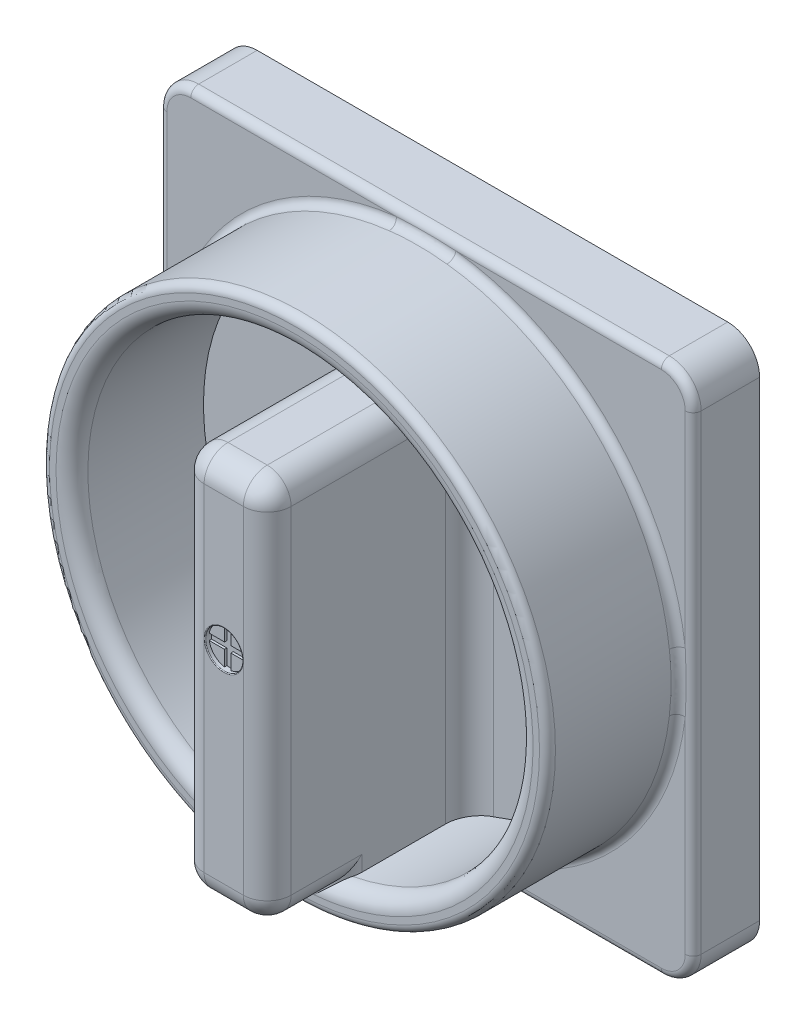
SolidWorks part; units mm, degrees
ref_plane "Front" through (0, 0, 0) normal (0, 0, 1) x (1, 0, 0)
ref_plane "Top" through (0, 0, 0) normal (0, 1, 0) x (1, 0, 0)
ref_plane "Right" through (0, 0, 0) normal (1, 0, 0) x (0, 0, -1)
sketch "Sketch1" plane through (0, 0, 0) normal (0, 0, 1) x (1, 0, 0)
  line L1 (-33.536, -33.536) -> (33.536, -33.536)
  line L2 (-33.536, -33.536) -> (-33.536, 33.536)
  line L3 (-33.536, 33.536) -> (33.536, 33.536)
  line L4 (33.536, -33.536) -> (33.536, 33.536)
  line L5 (-33.536, -33.536) -> (33.536, 33.536) construction
  line L6 (-33.536, 33.536) -> (33.536, -33.536) construction
  point P0 (0, 0)
  dimension "D1" = 67.072
  dimension "D2" = 67.072
extrude "Boss-Extrude1" add sketch "Sketch1" along normal blind 8.334
sketch "Sketch2" plane through (0, 0, 8.334) normal (0, 0, 1) x (1, 0, 0)
  circle A0 centre (0, 0) radius 31.75
  dimension "D1" = 63.5
extrude "Boss-Extrude2" add sketch "Sketch2" along normal blind 16.51
sketch "Sketch3" plane through (0, 0, 24.844) normal (0, 0, 1) x (1, 0, 0)
  circle A0 centre (0, 0) radius 27.94
  dimension "D1" = 55.88
extrude "Cut-Extrude1" cut sketch "Sketch3" against normal blind 16.51
sketch "Sketch4" plane through (0, 0, 8.334) normal (0, 0, 1) x (1, 0, 0)
  line L0 (0, 0) -> (0, 19.812) construction
  line L1 (-5.461, 19.812) -> (5.461, 19.812)
  line L2 (-5.461, 19.812) -> (-5.461, -28.448)
  line L3 (-5.461, -28.448) -> (5.461, -28.448)
  line L4 (5.461, 19.812) -> (5.461, -28.448)
  dimension "D1" = 19.812
  dimension "D2" = 10.922
  dimension "D3" = 48.26
extrude "Boss-Extrude3" add sketch "Sketch4" along normal blind 25.4
sketch "Sketch5" plane through (0, 0, 33.734) normal (0, 0, 1) x (1, 0, 0)
  circle A0 centre (0, 0) radius 2.35
  dimension "D1" = 4.7
extrude "Cut-Extrude2" cut sketch "Sketch5" against normal blind 0.5
sketch "Sketch6" plane through (0, 0, 33.734) normal (0, 0, 1) x (1, 0, 0)
  line L1 (-0.4, -2.3157) -> (0.4, -2.3157)
  line L2 (-0.4, -2.3157) -> (-0.4, 2.3157)
  line L3 (-0.4, 2.3157) -> (0.4, 2.3157)
  line L4 (0.4, -2.3157) -> (0.4, 2.3157)
  line L5 (-0.4, -2.3157) -> (0.4, 2.3157) construction
  line L6 (-0.4, 2.3157) -> (0.4, -2.3157) construction
  line L7 (-2.3157, 0.4) -> (2.3157, 0.4)
  line L8 (-2.3157, 0.4) -> (-2.3157, -0.4)
  line L9 (-2.3157, -0.4) -> (2.3157, -0.4)
  line L10 (2.3157, 0.4) -> (2.3157, -0.4)
  line L11 (-2.3157, 0.4) -> (2.3157, -0.4) construction
  line L12 (-2.3157, -0.4) -> (2.3157, 0.4) construction
  circle A0 centre (0, 0) radius 2.35 construction
  point P0 (0, 0)
  point P8 (0, 0)
  circle M5 centre (0, 0) radius 2.35
  dimension "D1" = 0.8
  dimension "D2" = 0.8
extrude "Cut-Extrude3" cut sketch "Sketch6" against normal blind 0.8 contours L8 L9 L2 L7 | L2 L7 L4 L3 | L2 L9 L4 L7 | L10 L7 L4 L9 | L9 L2 L1 L4 | L8 M5 | L3 M5 | L10 M5 | L1 M5 region at (0, -1.3579, 33.734) region at (0, -2.3294, 33.734) region at (-1.3579, 0, 33.734) region at (0, 0, 33.734) region at (-2.3294, 0, 33.734) region at (1.3579, 0, 33.734) region at (2.3294, 0, 33.734) region at (0, 1.3579, 33.734) region at (0, 2.3294, 33.734)
fillet "Fillet1" radius 4 4 edges at (33.536, -33.536, 4.167) (-33.536, -33.536, 4.167) (-33.536, 33.536, 4.167) (33.536, 33.536, 4.167)
fillet "Fillet2" radius 2 1 edges at (0, 27.94, 24.844)
fillet "Fillet3" radius 3 13 edges at (5.461, -3.7946, 8.334) (-5.461, -3.7946, 8.334) (5.461, 19.812, 21.034) (0, 19.812, 33.734) (-5.461, 19.812, 21.034) (0, 19.812, 8.334) (-5.461, -28.448, 29.289) (5.461, -28.448, 29.289) (0, -28.448, 33.734) (5.461, -4.318, 33.734) (-5.461, -4.318, 33.734) (5.461, -28.9429, 24.844) (-5.461, -28.9429, 24.844)
fillet "Fillet4" radius 1 9 edges at (32.3644, -32.3644, 8.334) (-32.3644, -32.3644, 8.334) (-32.3644, 32.3644, 8.334) (32.3644, 32.3644, 8.334) (0, 33.536, 8.334) (-33.536, 0, 8.334) (0, -33.536, 8.334) (33.536, 0, 8.334) (31.75, 0, 24.844)
fillet "Fillet5" radius 1 1 edges at (-31.75, 0, 8.334)
fillet "Fillet6" radius 0.1 1 edges at (2.35, 0, 33.734)
